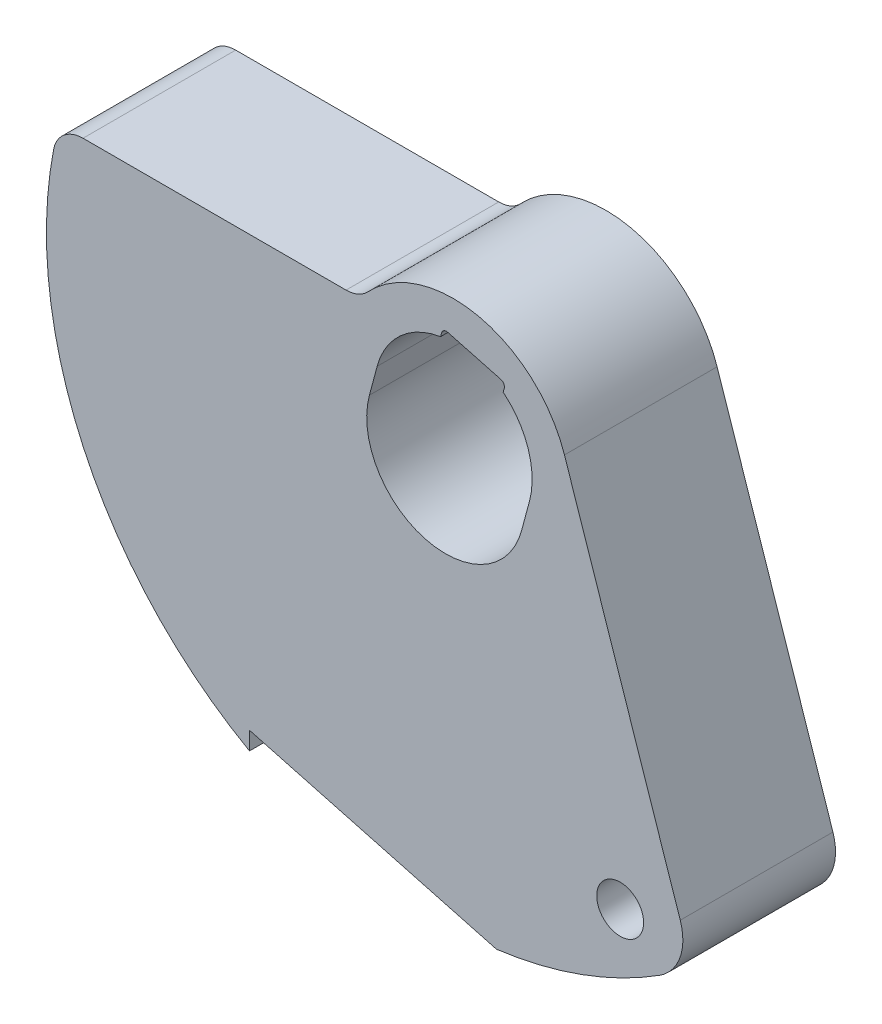
SolidWorks part; units mm, degrees
ref_plane "Front Plane" through (0, 0, 0) normal (0, 0, 1) x (1, 0, 0)
ref_plane "Top Plane" through (0, 0, 0) normal (0, 1, 0) x (1, 0, 0)
ref_plane "Right Plane" through (0, 0, 0) normal (1, 0, 0) x (0, 0, -1)
sketch "Sketch1" plane through (0, 0, 0) normal (0, 0, 1) x (1, 0, 0)
  line L0 (0, 40.7088) -> (0, -42.4788) construction
  line L1 (50.0011, 0) -> (-47.9361, 0) construction
  line L2 (0, 0) -> (4.815, 17.9697) construction
  line L3 (-7.4706, 2.0017) -> (6.4814, -1.7367) construction
  line L4 (-7.0762, 3.4738) -> (6.8758, -0.2646) construction
  line L5 (-3.8765, 1.0387) -> (-3.482, 2.5108)
  line L6 (4.2709, 0.4334) -> (3.8765, -1.0387)
  line L7 (-5.0653, 5.08) -> (-18.4566, 5.08)
  line L8 (6.0531, 3.3717) -> (7.0281, 0.4672)
  line L9 (12.9403, -3.6173) -> (17.147, -10.9034)
  line L10 (0, 0) -> (5.8427, -10.1199) construction
  line L11 (0, 0) -> (43.883, -11.7584) construction
  line L12 (8.89, 40.7088) -> (8.89, -42.4788) construction
  line L13 (50.0011, -15.24) -> (-47.9361, -15.24) construction
  line L14 (-1.0387, -3.8765) -> (-9.0244, -1.7367) construction
  line L15 (-9.9822, -16.7843) -> (-9.9822, -17.6991)
  line L16 (-9.9822, -16.7843) -> (2.5931, -20.1539)
  line L17 (2.8088, 5.0851) -> (0.11, 5.8082)
  line L18 (1.4594, 5.4467) -> (-6.5263, 7.5864) construction
  line L21 (2.9359, 4.578) -> (2.9884, 4.774)
  line L24 (-0.2536, 5.4326) -> (-0.2011, 5.6286)
  arc A0 (-3.8765, 1.0387) -> (3.8765, -1.0387) centre (0, 0) ccw
  arc A1 (6.1601, -0.0728) -> (6.1791, 0) centre (0.3944, 1.4721) ccw
  arc A2 (4.2709, 0.4334) -> (2.9359, 4.578) centre (0.3944, 1.4721) ccw
  arc A3 (7.0281, 0.4672) -> (12.6001, -3.4269) centre (12.446, 2.286) ccw
  arc A4 (6.0531, 3.3717) -> (-3.9548, 5.5602) centre (0.3944, 1.4721) ccw
  arc A5 (-19.953, 3.8443) -> (-9.9822, -17.6991) centre (0, 0) ccw
  arc A6 (12.6001, -3.4269) -> (12.9403, -3.6173) centre (12.6104, -3.8078) cw
  arc A7 (2.5931, -20.1539) -> (17.147, -10.9034) centre (0, 0) ccw
  arc A8 (-18.4566, 5.08) -> (-19.953, 3.8443) centre (-18.4566, 3.556) ccw
  arc A9 (-5.0653, 5.08) -> (-3.9548, 5.5602) centre (-5.0653, 6.604) ccw
  circle A10 centre (8.89, -15.24) radius 1.1938
  arc A11 (-0.2536, 5.4326) -> (-3.482, 2.5108) centre (0.3944, 1.4721) ccw
  arc A12 (2.8088, 5.0851) -> (2.9884, 4.774) centre (2.7431, 4.8397) cw
  arc A13 (-0.2011, 5.6286) -> (0.11, 5.8082) centre (0.0443, 5.5629) cw
  point P35 (-9.9822, 40.7088)
  point P36 (-9.9822, -42.4788)
  point P48 (1.5947, -0.4273)
  point P50 (6.4097, 17.5424)
  point P51 (-1.5947, 0.4273)
  point P52 (3.2202, 18.397)
  dimension "D1" = 8.0264
  dimension "D4" = 11.938
  dimension "D6" = 11.43
  dimension "D11" = 40.64
  dimension "D12" = 0.381
  dimension "D16" = 1.524
  dimension "D17" = 1.524
  dimension "D20" = 2.3876
  dimension "D24" = 0.254
  dimension "D2" = 15
  dimension "D5" = 5.08
  dimension "D7" = 2.286
  dimension "D8" = 12.446
  dimension "D9" = 60
  dimension "D10" = 9.398
  dimension "D13" = 15
  dimension "D14" = 18.796
  dimension "D15" = 9.9822
  dimension "D22" = 3.302
  dimension "D23" = 1.651
  dimension "D3" = 1.524
  dimension "D18" = 8.89
  dimension "D19" = 15.24
  dimension "D21" = 9.652
extrude "Boss-Extrude1" add sketch "Sketch1" against normal blind 7.7724 contours A9 L7 A8 A5 L15 L16 A7 L9 A6 A3 L8 A4 A10 A2 L6 A0 L5 region at (-3.0273, -7.1591, 0)
sketch "Sketch2" plane through (0, 0, 0) normal (0, 0, 1) x (1, 0, 0)
  line L0 (7.0281, 0.4672) -> (12.5499, -15.9813)
  arc A0 (2.5931, -20.1539) -> (17.147, -10.9034) centre (0, 0) ccw construction
extrude "Cut-Extrude1" cut sketch "Sketch2" against normal through all and the other way through all
fillet "Fillet1" radius 2.54 1 edges at (12.5499, -15.9813, -3.8862)
